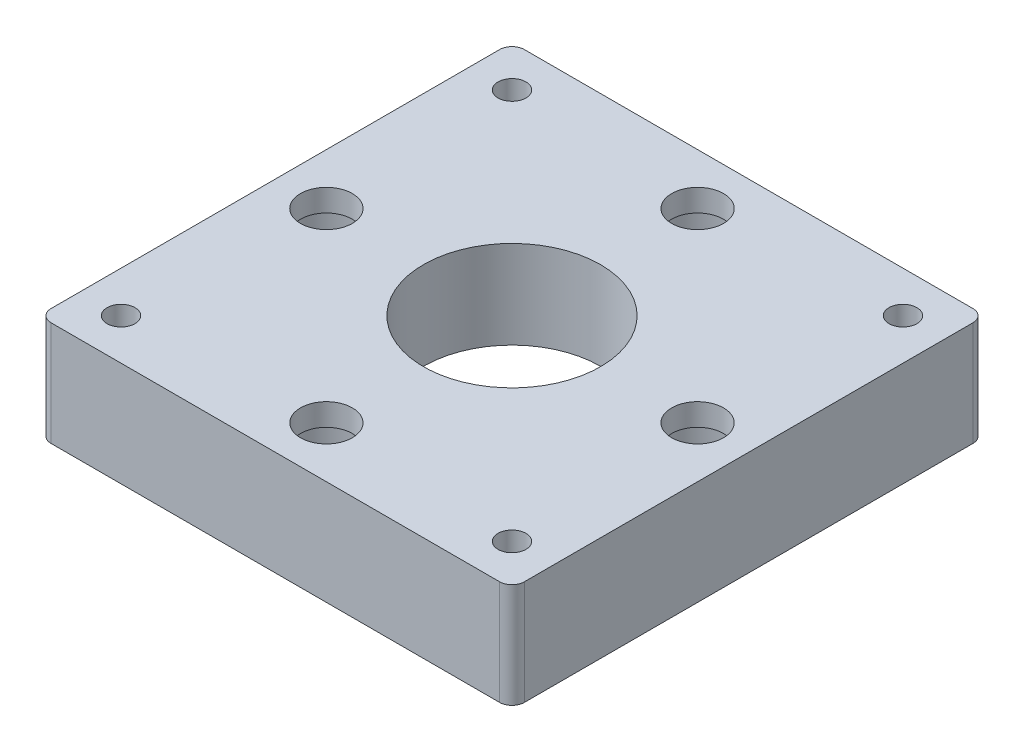
SolidWorks part; units mm, degrees
ref_plane "Alzado" through (0, 0, 0) normal (0, 0, 1) x (1, 0, 0)
ref_plane "Planta" through (0, 0, 0) normal (0, 1, 0) x (1, 0, 0)
ref_plane "Vista lateral" through (0, 0, 0) normal (1, 0, 0) x (0, 0, -1)
sketch "Croquis1" plane through (0, 0, 0) normal (0, 1, 0) x (1, 0, 0)
  line L0 (-28.75, 0) -> (28.75, 0) construction
  line L1 (0, 28.75) -> (0, -28.75) construction
  line L2 (-27.25, -28.75) -> (27.25, -28.75)
  line L3 (28.75, -27.25) -> (28.75, 27.25)
  line L4 (27.25, 28.75) -> (-27.25, 28.75)
  line L5 (-28.75, 27.25) -> (-28.75, -27.25)
  line L6 (-23.75, 23.75) -> (-23.75, 39.5688) construction
  line L7 (-23.75, 23.75) -> (-38.77, 23.75) construction
  circle A2 centre (-23.75, 23.75) radius 1.6938
  circle A3 centre (23.75, 23.75) radius 1.6938
  circle A4 centre (23.75, -23.75) radius 1.6938
  circle A5 centre (-23.75, -23.75) radius 1.6938
  arc A7 (-27.25, -28.75) -> (-28.75, -27.25) centre (-27.25, -27.25) cw
  arc A8 (27.25, -28.75) -> (28.75, -27.25) centre (27.25, -27.25) ccw
  arc A9 (28.75, 27.25) -> (27.25, 28.75) centre (27.25, 27.25) ccw
  arc A10 (-28.75, 27.25) -> (-27.25, 28.75) centre (-27.25, 27.25) cw
  point P26 (-28.75, -28.75)
  point P29 (28.75, -28.75)
  point P32 (28.75, 28.75)
  dimension "D4" = 0
  dimension "D6" = 1.5
  dimension "D1" = 57.5
  dimension "D2" = 57.5
  dimension "D3" = 5
  dimension "D5" = 5
  dimension "D7" = 0
extrude "Saliente-Extruir1" add sketch "Croquis1" along normal blind 12.7 contours L4 A10 L5 A7 L2 A8 L3 A9
extrude "Cortar-Extruir1" cut sketch "Croquis1<4>" along normal blind 29.7 flip side to cut
sketch "Croquis1<4>" plane through (0, 0, 0) normal (0, 1, 0) x (1, 0, 0) same geometry as "Croquis1"
sketch "Croquis2" plane through (0, 0, 0) normal (0, -1, 0) x (1, 0, 0)
  line L0 (-28.75, 0) -> (28.75, 0) construction
  circle A0 centre (0, 0) radius 19
extrude "Cortar-Extruir2" cut sketch "Croquis2" against normal blind 2 contours A0
sketch "Croquis3" plane through (0, 2, 0) normal (0, -1, 0) x (1, 0, 0)
  line L0 (-28.75, 0) -> (28.75, 0) construction
  circle A0 centre (0, 0) radius 10.75
extrude "Cortar-Extruir3" cut sketch "Croquis3" against normal through all contours A0
sketch "Croquis4" plane through (0, 0, 0) normal (0, -1, 0) x (1, 0, 0)
  line L0 (22.55, 0) -> (22.55, 20.4352) construction
  line L1 (-28.75, 0) -> (28.75, 0) construction
  line L3 (28.75, 27.25) -> (28.75, -27.25) construction
  line L4 (0, 30.2397) -> (0, -28.7519) construction
  line L5 (-29.0422, 0) -> (28.4578, 0) construction
  circle A0 centre (22.55, 0) radius 5.5
  circle A1 centre (0, -22.55) radius 5.5
  circle A2 centre (-22.55, 0) radius 5.5
  circle A3 centre (0, 22.55) radius 5.5
  point P21 (0, 0)
  dimension "D1" = 6.2
  dimension "D2" = 0
  dimension "D3" = 0
  dimension "D4" = 4
extrude "Cortar-Extruir4" cut sketch "Croquis4" against normal blind 10 contours A3 | A2 | A0 | A1
sketch "Croquis6" plane through (0, 10, 0) normal (0, -1, 0) x (1, 0, 0)
  circle A0 centre (22.55, 0) radius 3.15
  circle A1 centre (0, -22.55) radius 3.15
  circle A2 centre (-22.55, 0) radius 3.15
  circle A3 centre (0, 22.55) radius 3.15
  point P12 (0, 0)
  dimension "D1" = 4
extrude "Cortar-Extruir5" cut sketch "Croquis6" against normal through all
